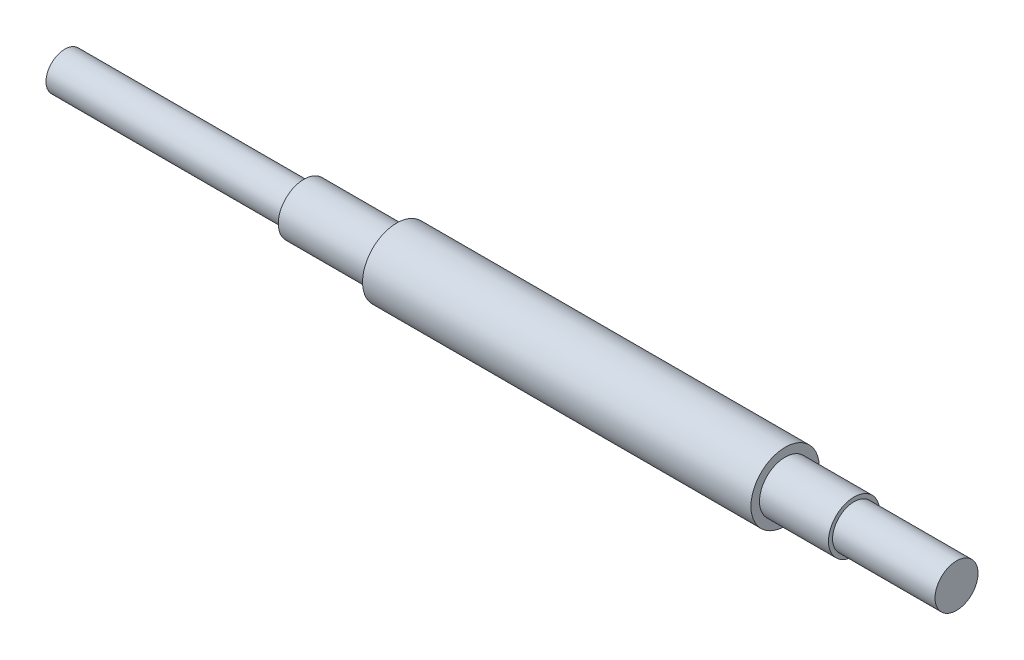
SolidWorks part; units mm, degrees
ref_plane "Front Plane" through (0, 0, 0) normal (0, 0, 1) x (1, 0, 0)
ref_plane "Top Plane" through (0, 0, 0) normal (0, 1, 0) x (1, 0, 0)
ref_plane "Right Plane" through (0, 0, 0) normal (1, 0, 0) x (0, 0, -1)
sketch "Sketch1" plane through (0, 0, 0) normal (0, 1, 0) x (1, 0, 0)
  line L0 (-78.6306, 0) -> (87.1662, 0) construction
  line L1 (-78.6306, 0) -> (-78.6306, 3.5)
  line L2 (-78.6306, 3.5) -> (-34.1806, 3.5)
  line L3 (-34.1806, 3.5) -> (-34.1806, 4.7625)
  line L4 (-34.1806, 4.7625) -> (-16.9251, 4.7625)
  line L5 (-16.9251, 4.7625) -> (-16.9251, 6.35)
  line L6 (-16.9251, 6.35) -> (55.2948, 6.35)
  line L7 (55.2948, 6.35) -> (55.2948, 4.7625)
  line L8 (55.2948, 4.7625) -> (68.1162, 4.7625)
  line L9 (68.1162, 4.7625) -> (68.1162, 3.9992)
  line L10 (68.1162, 3.9992) -> (87.1662, 3.9992)
  line L11 (87.1662, 3.9992) -> (87.1662, 0)
  line L12 (-78.6306, 0) -> (87.1662, 0)
  line L13 (-97.9506, 0) -> (194.5593, 0) construction
  dimension "D1" = 7
  dimension "D2" = 9.525
  dimension "D3" = 9.525
  dimension "D4" = 7.9985
  dimension "D5" = 44.45
  dimension "D6" = 17.2554
  dimension "D7" = 12.8214
  dimension "D8" = 19.05
  dimension "D9" = 72.22
  dimension "D10" = 6.35
revolve "Revolve1" add sketch "Sketch1" angle 360 about L13
